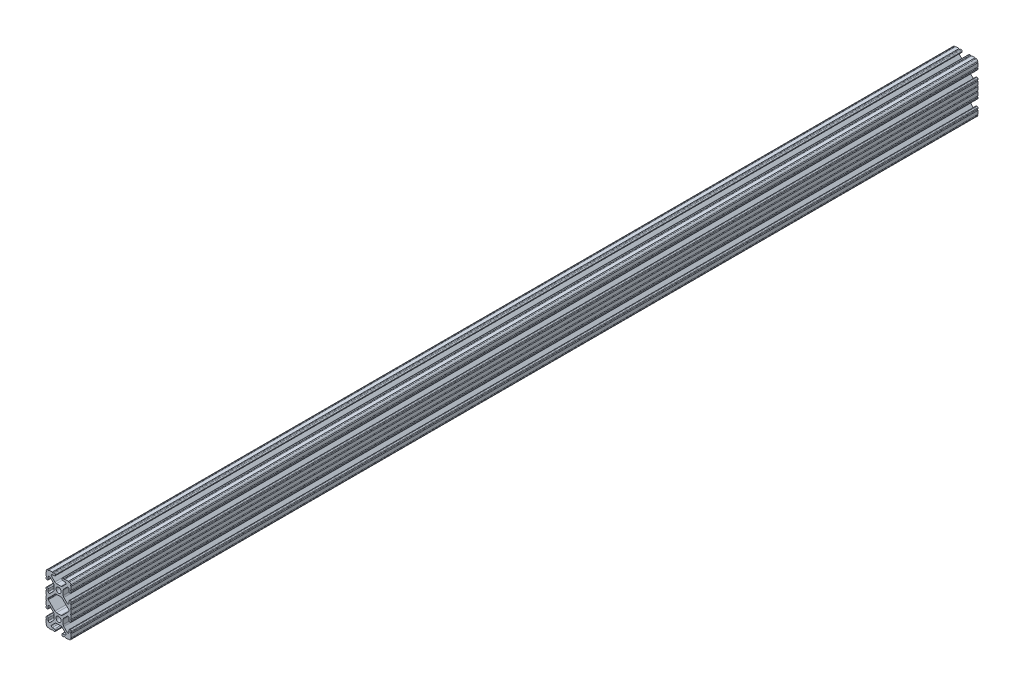
SolidWorks part; units mm, degrees
ref_plane "Front Plane" through (0, 0, 0) normal (0, 0, 1) x (1, 0, 0)
ref_plane "Top Plane" through (0, 0, 0) normal (0, 1, 0) x (1, 0, 0)
ref_plane "Right Plane" through (0, 0, 0) normal (1, 0, 0) x (0, 0, -1)
sketch "Sketch2" plane through (0, 0, 0) normal (0, 0, 1) x (1, 0, 0)
  line L0 (0, 25.4) -> (0, -25.4) construction
  line L1 (-12.7, 0) -> (12.7, 0) construction
  line L2 (3.2512, -25.4) -> (12.7, -25.4)
  line L3 (12.7, -25.4) -> (12.7, -15.9512)
  line L4 (3.2512, -25.4) -> (3.2512, -23.1902)
  line L5 (3.2512, -23.1902) -> (8.9276, -23.1902)
  line L6 (8.9276, -23.1902) -> (3.0856, -17.3482)
  line L7 (0, -12.7) -> (12.7, -25.4) construction
  line L8 (12.7, -15.9512) -> (10.4902, -15.9512)
  line L9 (10.4902, -15.9512) -> (10.4902, -21.6276)
  line L10 (10.4902, -21.6276) -> (4.6482, -15.7856)
  line L11 (3.2512, -25.4) -> (0, -25.4) construction
  line L12 (0, -25.4) -> (-3.2512, -25.4) construction
  line L13 (-3.2512, -25.4) -> (-12.7, -25.4) construction
  line L14 (12.7, 25.4) -> (-12.7, 25.4) construction
  line L15 (0, 12.7) -> (0, -12.7) construction
  circle A0 centre (0, -12.7) radius 2.6035
  arc A1 (6.3485, -23.1902) -> (7.1039, -21.3665) centre (6.3485, -22.1219) ccw construction
  point P8 (0, -17.3482)
  point P16 (-2.6035, -12.7)
  point P18 (2.6035, -12.7)
  point P19 (0, -10.0965)
  point P20 (0, -15.3035)
  point P27 (-12.7, -25.4)
  point P30 (0, 25.4)
  point P31 (12.7, 25.4)
  point P32 (-12.7, 25.4)
  point P33 (12.7, -25.4)
  point P34 (0, -12.7)
  point P35 (0, 12.7)
  point P37 (0, 0)
  point P38 (-3.2512, -25.4)
  point P39 (3.2512, -25.4)
  dimension "Center Hole Diameter" = 5.207
  dimension "Rail Height" = 50.8
  dimension "Rail Width" = 25.4
  dimension "T-Slot Width" = 6.5024
  dimension "Slot Inner Width" = 14.8336
  dimension "Thickness" = 2.2098
  dimension "Slot Depth" = 5.842
  dimension "D1" = 2.2098
  dimension "C to C" = 25.4
sketch "Sketch3" plane through (0, 0, 0) normal (1, 0, 0) x (0, 0, -1)
  line L0 (-457.2, -25.4) -> (457.2, -25.4) construction
  line L1 (-406.4, 0) -> (406.4, 0) construction
  point P6 (-457.2, -25.4)
  point P8 (-406.4, 0)
  point P9 (406.4, 0)
  point P10 (457.2, -25.4)
  dimension "Length" = 914.4
sketch "Sketch4" plane through (0, 0, 0) normal (0, 0, 1) x (1, 0, 0)
  line L0 (4.1904, -25.4) -> (10.1173, -25.4)
  line L1 (3.2512, -25.4) -> (12.7, -25.4) construction
  line L2 (3.2512, -25.4) -> (3.2512, -23.1902) construction
  line L3 (3.2512, -23.1902) -> (8.9276, -23.1902) construction
  line L4 (3.2512, -24.1294) -> (3.2512, -24.4608)
  line L5 (4.1904, -23.1902) -> (6.3485, -23.1902)
  line L6 (0, -17.3482) -> (2.164, -17.3482)
  line L7 (8.9276, -23.1902) -> (3.0856, -17.3482) construction
  line L8 (3.7373, -17.9999) -> (7.1039, -21.3665)
  line L9 (12.7, -25.4) -> (12.7, -15.9512) construction
  line L10 (10.4902, -21.6276) -> (4.6482, -15.7856) construction
  line L11 (10.4902, -15.9512) -> (10.4902, -21.6276) construction
  line L12 (10.4902, -19.0485) -> (10.4902, -16.8904)
  line L13 (12.7, -15.9512) -> (10.4902, -15.9512) construction
  line L14 (11.4294, -15.9512) -> (11.7608, -15.9512)
  line L15 (12.7, -16.8904) -> (12.7, -22.8173)
  line L16 (8.6665, -19.8039) -> (5.2999, -16.4373)
  line L17 (4.6482, -12.7) -> (4.6482, -14.864)
  line L19 (0, -17.3482) -> (0, -15.3035)
  line L20 (0, 25.4) -> (0, -25.4) construction
  line L21 (4.6482, -12.7) -> (2.6035, -12.7)
  arc A0 (3.2512, -24.4608) -> (4.1904, -25.4) centre (4.1904, -24.4608) ccw
  circle A1 centre (0, -12.7) radius 2.6035 construction
  arc A2 (3.2512, -24.1294) -> (4.1904, -23.1902) centre (4.1904, -24.1294) cw
  arc A3 (6.3485, -23.1902) -> (7.1039, -21.3665) centre (6.3485, -22.1219) ccw
  arc A4 (2.164, -17.3482) -> (3.7373, -17.9999) centre (2.164, -19.5732) cw
  arc A5 (10.1173, -25.4) -> (12.7, -22.8173) centre (10.1173, -22.8173) ccw
  arc A6 (8.6665, -19.8039) -> (10.4902, -19.0485) centre (9.4219, -19.0485) ccw
  arc A7 (10.4902, -16.8904) -> (11.4294, -15.9512) centre (11.4294, -16.8904) cw
  arc A8 (11.7608, -15.9512) -> (12.7, -16.8904) centre (11.7608, -16.8904) cw
  arc A9 (5.2999, -16.4373) -> (4.6482, -14.864) centre (6.8732, -14.864) cw
  arc A11 (0, -15.3035) -> (2.6035, -12.7) centre (0, -12.7) ccw
  dimension "D1" = 2.5827
  dimension "D2" = 2.225
  dimension "D3" = 0.9392
extrude "Boss-Extrude1" add sketch "Sketch4" along normal mid plane 914.4
sketch "Sketch5" plane through (0, 0, 0) normal (0, 0, 1) x (1, 0, 0)
  line L0 (3.2512, -25.4) -> (12.7, -25.4) construction
  line L1 (4.1904, -23.1902) -> (6.3485, -23.1902) construction
  line L3 (0, -12.7) -> (12.7, -25.4) construction
  line L4 (6.3485, -23.1902) -> (6.3485, -25.4) construction
  line L5 (8.9276, -23.1902) -> (3.0856, -17.3482) construction
  circle A0 centre (10.3562, -25.4) radius 0.5524
  circle A1 centre (5.796, -25.4) radius 0.5524
  circle A2 centre (12.7, -23.0562) radius 0.5524
  circle A3 centre (12.7, -18.496) radius 0.5524
  point P10 (5.2694, -23.1902)
  point P12 (9.4219, -19.0485)
  dimension "D1" = 1.1049
extrude "Cut-Extrude1" cut sketch "Sketch5" against normal through all both and the other way through all
mirror "Mirror1" about plane through (4.6482, -12.7, 457.2) normal (0, -1, 0) of bodies 137 134
sketch "Sketch6" plane through (0, 0, 0) normal (0, 0, 1) x (1, 0, 0)
  line L0 (12.7, -1.7914) -> (12.7, 0)
  line L1 (12.7, 0) -> (9.8037, 0)
  line L2 (-12.7, 0) -> (12.7, 0) construction
  line L3 (9.8037, 0) -> (9.8037, -2.3438)
  line L4 (9.8037, -2.3438) -> (12.1476, -2.3438)
  circle A0 centre (12.7, -2.3438) radius 0.5524 construction
  arc A1 (12.7, -1.7914) -> (12.1476, -2.3438) centre (12.7, -2.3438) ccw
  arc A4 (12.58, -1.8046) -> (12.7, -2.8963) centre (12.7, -2.3438) ccw construction
  arc A6 (9.8037, 0) -> (10.8954, -0.12) centre (10.3562, 0) ccw construction
extrude "Boss-Extrude2" add sketch "Sketch6" along normal mid plane 914.4
sketch "Sketch7" plane through (0, 0, 0) normal (0, 0, 1) x (1, 0, 0)
  line L0 (5.4206, -5.7168) -> (10.3284, -0.809)
  line L1 (3.7373, -7.4001) -> (7.1039, -4.0335) construction
  line L2 (10.4902, -0.4184) -> (10.4902, 0)
  line L3 (0, 0) -> (10.4902, 0)
  line L4 (-12.7, 0) -> (12.7, 0) construction
  line L5 (0, 0) -> (5.4206, -5.7168)
  arc A0 (10.3284, -0.809) -> (10.4902, -0.4184) centre (9.9377, -0.4184) ccw
  arc A3 (12.7, -1.7914) -> (12.7, -2.8963) centre (12.7, -2.3438) ccw construction
extrude "Cut-Extrude2" cut sketch "Sketch7" against normal through all both and the other way through all
mirror "Mirror2" about plane through (0, 0, 0) normal (0, 1, 0) of bodies 139 135
mirror "Mirror3" about plane through (0, 0, 0) normal (1, 0, 0) of bodies 136
equation "\"D1@Boss-Extrude1\"=\"Length@Sketch3\""
equation "\"D1@Sketch2\"=\"Thickness@Sketch2\""
equation "\"D2@Sketch4\"=\"Slot Inner Width@Sketch2\"*0.15"
equation "\"D1@Sketch4\"=\"D3@Sketch4\"*2.75"
equation "\"D3@Sketch4\"=\"Thickness@Sketch2\"*0.425"
equation "\"D1@Sketch5\"=\"Thickness@Sketch2\"*0.5"
equation "\"D1@Boss-Extrude2\"=\"Length@Sketch3\""
